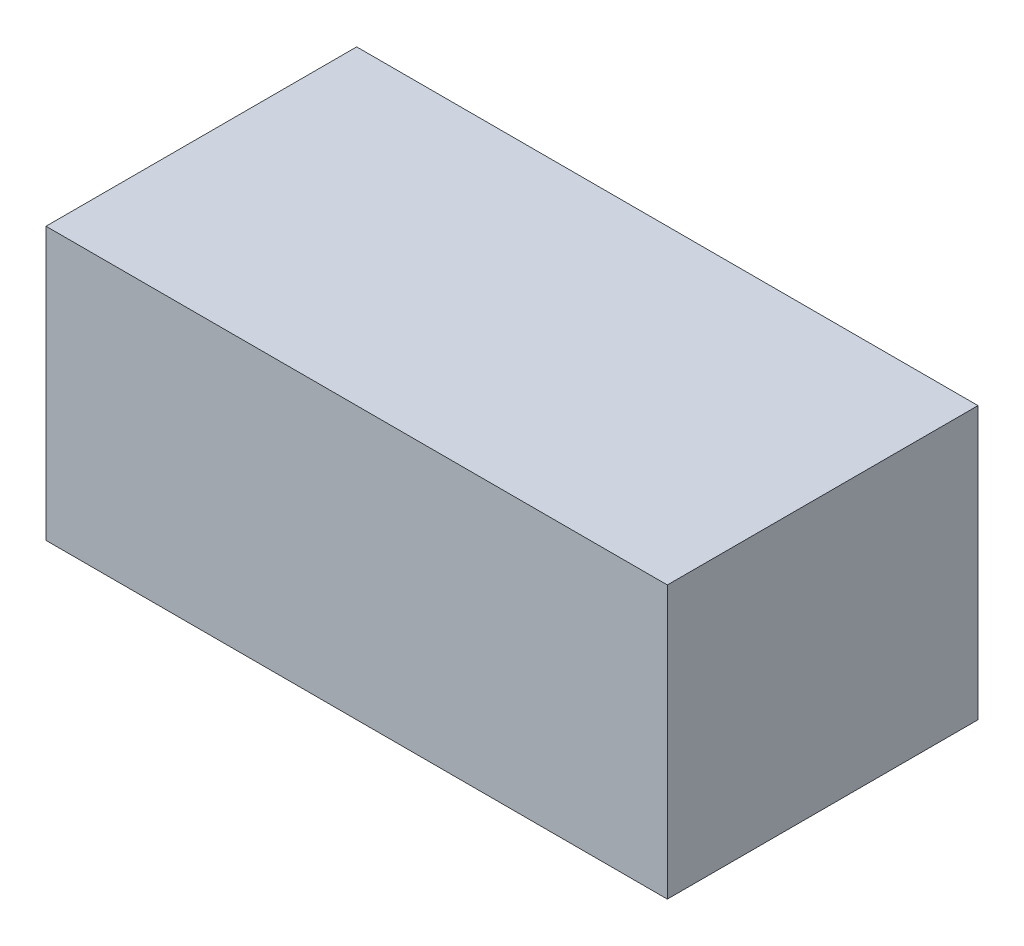
SolidWorks part; units mm, degrees
ref_plane "Front Plane" through (0, 0, 0) normal (0, 0, 1) x (1, 0, 0)
ref_plane "Top Plane" through (0, 0, 0) normal (0, 1, 0) x (1, 0, 0)
ref_plane "Right Plane" through (0, 0, 0) normal (1, 0, 0) x (0, 0, -1)
sketch "Sketch4" plane through (0, 0, 0) normal (0, 1, 0) x (1, 0, 0)
  line L1 (-145, 72.5) -> (145, 72.5)
  line L2 (-145, 72.5) -> (-145, -72.5)
  line L3 (-145, -72.5) -> (145, -72.5)
  line L4 (145, 72.5) -> (145, -72.5)
  line L5 (-145, 72.5) -> (145, -72.5) construction
  line L6 (-145, -72.5) -> (145, 72.5) construction
  point P0 (0, 0)
  dimension "D1" = 145
  dimension "D2" = 290
extrude "Boss-Extrude3" add sketch "Sketch4" along normal blind 127
sketch "Sketch5" plane through (0, 0, 0) normal (0, 1, 0) x (1, 0, 0)
  line L0 (-145, 72.5) -> (-145, -72.5) construction
  line L1 (-143, 70.5) -> (143, 70.5)
  line L2 (-143, 70.5) -> (-143, -70.5)
  line L3 (-143, -70.5) -> (143, -70.5)
  line L4 (143, 70.5) -> (143, -70.5)
  line L5 (145, 72.5) -> (-145, 72.5) construction
  line L6 (-145, -72.5) -> (145, -72.5) construction
  line L7 (145, -72.5) -> (145, 72.5) construction
  dimension "D1" = 2
  dimension "D2" = 2
  dimension "D3" = 2
  dimension "D4" = 2
extrude "Cut-Extrude2" cut sketch "Sketch5" along normal blind 126.8
